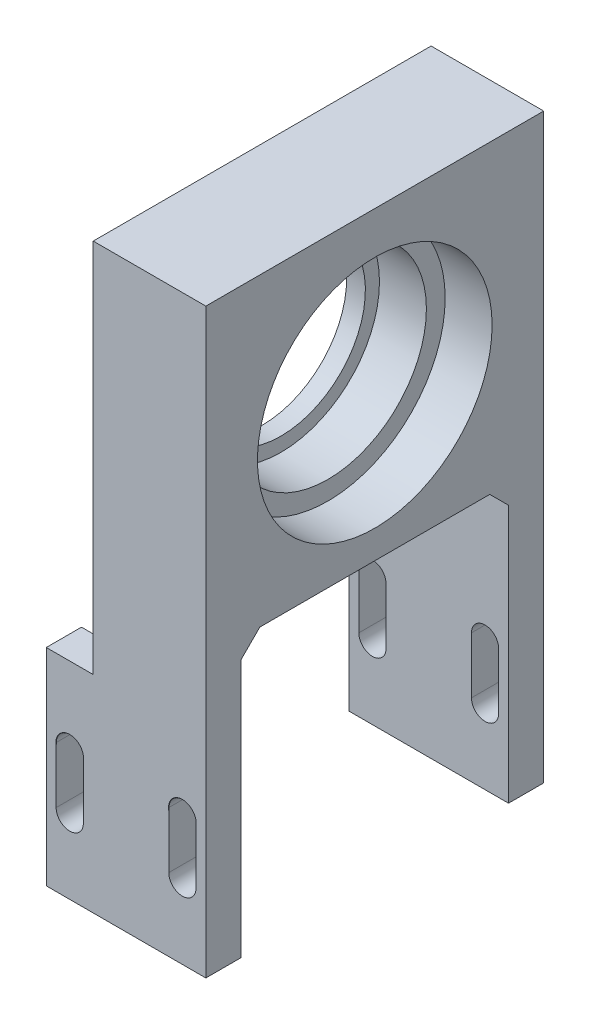
SolidWorks part; units mm, degrees
material "6061 Alloy"
ref_plane "Front Plane" through (0, 0, 0) normal (0, 0, 1) x (1, 0, 0)
ref_plane "Top Plane" through (0, 0, 0) normal (0, 1, 0) x (1, 0, 0)
ref_plane "Right Plane" through (0, 0, 0) normal (1, 0, 0) x (0, 0, -1)
sketch "Sketch1" plane through (0, 0, 0) normal (0, 0, 1) x (1, 0, 0)
  line L0 (0, 0) -> (17, 0)
  line L1 (17, 0) -> (17, 29)
  line L3 (17, 29) -> (17, 62)
  line L4 (17, 62) -> (5, 62)
  line L5 (5, 62) -> (5, 22)
  line L6 (5, 22) -> (0, 22)
  line L7 (0, 22) -> (0, 0)
  point P8 (0, 0)
  dimension "D1" = 17
  dimension "D2" = 62
  dimension "D3" = 22
  dimension "D4" = 12
extrude "Boss-Extrude1" add sketch "Sketch1" along normal blind 36
sketch "Sketch2" plane through (17, 0, 0) normal (1, 0, 0) x (0, 0, -1)
  line L0 (-18, 62) -> (-18, 12.1467) construction
  line L1 (-36, 62) -> (0, 62) construction
  circle A0 centre (-18, 45) radius 10.5
  dimension "D1" = 21
  dimension "D2" = 17
extrude "Cut-Extrude1" cut sketch "Sketch2" against normal through all
sketch "Sketch3" plane through (17, 0, 0) normal (1, 0, 0) x (0, 0, -1)
  line L0 (-36, 0) -> (0, 0) construction
  line L1 (-32.25, 0) -> (-3.75, 0)
  line L2 (-32.25, 0) -> (-32.25, 29.5)
  line L3 (-32.25, 29.5) -> (-3.75, 29.5)
  line L4 (-3.75, 0) -> (-3.75, 29.5)
  line L6 (-18, 0) -> (-18, 45) construction
  dimension "D1" = 28.5
  dimension "D2" = 29.5
extrude "Cut-Extrude2" cut sketch "Sketch3" against normal through all
chamfer "Chamfer1" distance 2 angle 45 2 edges at (11, 29.5, 32.25) (11, 29.5, 3.75)
sketch "Sketch6" plane through (5, 0, 0) normal (-1, 0, 0) x (0, 0, 1)
  circle A0 centre (18, 45) radius 10.5 construction
  circle A1 centre (18, 45) radius 10.5
  circle A2 centre (18, 45) radius 9
  dimension "D1" = 1.5
extrude "Boss-Extrude2" add sketch "Sketch6" against normal blind 2
sketch "Sketch10" plane through (5, 0, 0) normal (-1, 0, 0) x (0, 0, 1)
  circle A0 centre (18, 45) radius 11
  circle A1 centre (18, 45) radius 15
  dimension "D1" = 22
  dimension "D2" = 30
extrude "Cut-Extrude4" cut sketch "Sketch10" against normal blind 0.6
sketch "Sketch11" plane through (17, 0, 0) normal (1, 0, 0) x (0, 0, -1)
  circle A0 centre (-18, 45) radius 12.5
  dimension "D1" = 25
extrude "Cut-Extrude5" cut sketch "Sketch11" against normal blind 5
sketch "Sketch14" plane through (0, 0, 36) normal (0, 0, 1) x (1, 0, 0)
  line L0 (2.5, 13.75) -> (14.5, 13.75)
  line L3 (8.5, 13.75) -> (8.5, 0)
  line L4 (0, 0) -> (17, 0) construction
  line L5 (5, 29.5) -> (17, 29.5) construction
  point P0 (14.5, 13.75)
  point P2 (2.5, 13.75)
  dimension "D1" = 15.75
  dimension "D2" = 12
hole_wizard "M2.5 Clearance Hole1" positions "Sketch14" profile "Sketch13" hole size "M2.5" standard "DIN" end condition through all
sketch "Sketch13" plane through (14.5, 13.75, 36) normal (1, 0, 0) x (0, -1, 0)
  line L0 (0, 0) -> (0, 36)
  line L1 (0, 36) -> (1.45, 36)
  line L2 (1.45, 36) -> (1.45, 0.025)
  line L3 (1.45, 0.025) -> (1.475, 0)
  line L5 (1.475, 0) -> (0, 0)
  line L6 (-1.45, 0.025) -> (-1.475, 0) construction
  line L11 (0, -6.35) -> (0, 107.95) construction
  dimension "Thru Hole Dia." = 2.9
  dimension "Thru Hole Depth" = 36
  dimension "Near C'Sink Dia." = 2.95
  dimension "Near C'Sink Angle" = 90
sketch "Sketch15" plane through (0, 0, 0) normal (0, 0, -1) x (-1, 0, 0)
  line L0 (-14.5, 13.75) -> (-14.5, 7.75) construction
  line L1 (-13.05, 13.75) -> (-13.05, 7.75)
  line L2 (-15.95, 13.75) -> (-15.95, 7.75)
  line L3 (-2.5, 13.75) -> (-2.5, 7.75) construction
  line L4 (-1.05, 13.75) -> (-1.05, 7.75)
  line L5 (-3.95, 13.75) -> (-3.95, 7.75)
  arc A0 (-13.05, 13.75) -> (-15.95, 13.75) centre (-14.5, 13.75) ccw
  arc A1 (-15.95, 7.75) -> (-13.05, 7.75) centre (-14.5, 7.75) ccw
  arc A2 (-1.05, 13.75) -> (-3.95, 13.75) centre (-2.5, 13.75) ccw
  arc A3 (-3.95, 7.75) -> (-1.05, 7.75) centre (-2.5, 7.75) ccw
  circle A4 centre (-14.5, 13.75) radius 1.45 construction
  point P3 (-14.5, 10.75)
  point P8 (-2.5, 10.75)
  dimension "D1" = 6
extrude "Cut-Extrude6" cut sketch "Sketch15" against normal through all
sketch "Sketch16" plane through (0, 0, 0) normal (0, 0, -1) x (-1, 0, 0)
  line L0 (0, 22) -> (-5, 32)
  line L1 (-5, 62) -> (-5, 22) construction
  dimension "D1" = 10
rib "Rib6" [suppressed] sketch "Sketch16" sketch "Sketch16" thickness 3.75 extrusion direction parallel to sketch draft on no parameters "D1"=3.75
